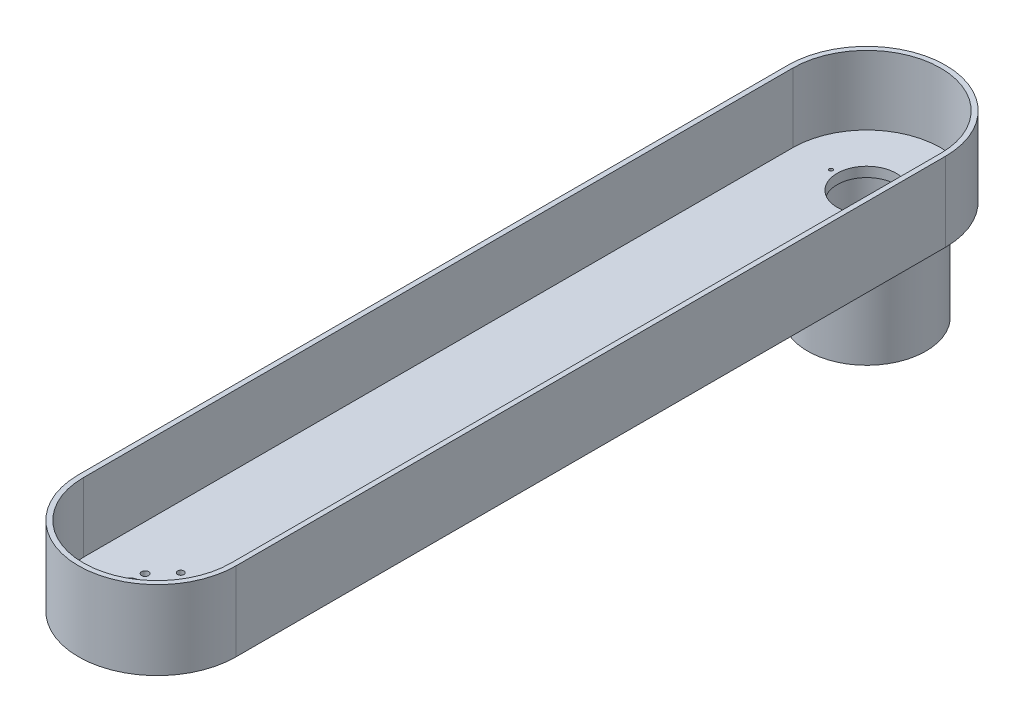
SolidWorks part; units mm, degrees
material "ABS"
ref_plane "Front Plane" through (0, 0, 0) normal (0, 0, 1) x (1, 0, 0)
ref_plane "Top Plane" through (0, 0, 0) normal (0, 1, 0) x (1, 0, 0)
ref_plane "Right Plane" through (0, 0, 0) normal (1, 0, 0) x (0, 0, -1)
sketch "Sketch1" plane through (0, 0, 0) normal (0, 1, 0) x (1, 0, 0)
  circle A0 centre (0, 0) radius 34.925
  circle A1 centre (0, 0) radius 38.1
  dimension "D1" = 69.85
  dimension "D2" = 3.175
extrude "Boss-Extrude1" add sketch "Sketch1" along normal blind 51.435
sketch "Sketch6" plane through (0, 0, 0) normal (0, -1, 0) x (1, 0, 0)
  circle A2 centre (0, 0) radius 34.925
  circle A3 centre (0, 0) radius 34.925
  circle A5 centre (0, 0) radius 38.1
  circle A6 centre (0, 0) radius 38.1
  dimension "D1" = 0
  dimension "D2" = 0
extrude "Boss-Extrude5" add sketch "Sketch6" along normal blind 6.096
ref_plane "Plane2" through (0, 23.114, 0) normal (0, -1, 0) x (1, 0, 0)
sketch "Sketch12" plane through (0, 23.114, 0) normal (0, -1, 0) x (1, 0, 0)
  circle A0 centre (0, 0) radius 25.4
  circle A5 centre (0, 0) radius 34.925
  dimension "D1" = 50.8
  dimension "D2" = 69.85
extrude "Boss-Extrude8" add sketch "Sketch12" against normal up to surface (28.321 mm away) up to face at (0, 51.435, 38.1)
sketch "Sketch2" plane through (0, 51.435, 0) normal (0, 1, 0) x (1, 0, 0)
  circle A0 centre (0, 0) radius 19.05
  circle A3 centre (0, 0) radius 38.1
  circle A4 centre (0, 0) radius 38.1
  dimension "D1" = 38.1
  dimension "D2" = 0
extrude "Boss-Extrude2" add sketch "Sketch2" along normal blind 6.35
ref_plane "Plane1" through (0, 26.67, 0) normal (0, -1, 0) x (1, 0, 0)
sketch "Sketch4" plane through (0, 26.67, 0) normal (0, -1, 0) x (1, 0, 0)
  circle A0 centre (0, 0) radius 26.9494
  dimension "D1" = 53.8988
extrude "Cut-Extrude1" cut sketch "Sketch4" along normal blind 1.7272
sketch "Sketch5" plane through (0, 57.785, 0) normal (0, 1, 0) x (1, 0, 0)
  line L0 (0, 0) -> (0, 12.0132) construction
  circle A0 centre (-23.0124, 0) radius 1.1303
  circle A1 centre (23.0124, 0) radius 1.1303
  dimension "D1" = 2.2606
  dimension "D2" = 46.0248
  dimension "D3" = 23.0124
extrude "Cut-Extrude5" cut sketch "Sketch5" against normal through all
cosmetic thread "Cosmetic Thread1" parameters "D2"=2.8448
cosmetic thread "Cosmetic Thread2" parameters "D2"=2.8448
sketch "Sketch7" plane through (0, 57.785, 0) normal (0, 1, 0) x (1, 0, 0)
  line L2 (-50.8, 0) -> (-50.8, -457.2)
  line L4 (50.8, 0) -> (50.8, -457.2)
  arc A0 (50.8, 0) -> (-50.8, 0) centre (0, 0) ccw
  arc A1 (-50.8, -457.2) -> (50.8, -457.2) centre (0, -457.2) ccw
  circle A5 centre (0, 0) radius 38.1
  circle A6 centre (0, 0) radius 38.1
  dimension "D1" = 101.6
  dimension "D2" = 457.2
  dimension "D3" = 0
extrude "Boss-Extrude6" add sketch "Sketch7" along normal blind 44.45 and the other way blind 6.35 separate body
shell "Shell3" thickness 3.175 removed face at (0, 102.235, 228.6)
sketch "Sketch11" plane through (0, 57.785, 0) normal (0, 1, 0) x (1, 0, 0)
  circle A2 centre (0, 0) radius 41.275
  circle A3 centre (0, 0) radius 41.275
  dimension "D1" = 0
extrude "Cut-Extrude4" cut sketch "Sketch11" along normal through all
combine bodies "Combine2" operation type add bodies to combine 116 120
sketch "Sketch13" plane through (0, 51.435, 0) normal (0, -1, 0) x (1, 0, 0)
  circle A0 centre (0, 457.2) radius 11
  circle A1 centre (0, 457.2) radius 21.5 construction
  circle A2 centre (0, 478.7) radius 2.25
  circle A3 centre (18.6195, 446.45) radius 2.25
  circle A4 centre (-18.6195, 446.45) radius 2.25
  circle A5 centre (0, 457.2) radius 17.5 construction
  circle A6 centre (-17.5, 457.2) radius 6
  circle A7 centre (17.5, 457.2) radius 6
  dimension "D1" = 22
  dimension "D2" = 43
  dimension "D3" = 4.5
  dimension "D5" = 35
  dimension "D6" = 12
  dimension "D7" = 12
  dimension "D4" = 3
extrude "Cut-Extrude6" cut sketch "Sketch13" against normal through all
sketch "Sketch15" plane through (0, 51.435, 0) normal (0, -1, 0) x (1, 0, 0)
  circle A2 centre (-17.5, 457.2) radius 6
  circle A3 centre (-17.5, 457.2) radius 6
  circle A5 centre (17.5, 457.2) radius 6
  circle A6 centre (17.5, 457.2) radius 6
  dimension "D1" = 0
  dimension "D2" = 0
extrude "Extrude-Thin1" add sketch "Sketch15" against normal up to surface (6.35 mm away) from offset 3.5 thin up to face at (17.5, 57.785, 463.2) offset against normal yes thin type one direction reverse wall 1
chamfer "Chamfer1" distance 2.3 angle 45 3 edges at (18.6195, 51.435, 444.2) (-18.6195, 51.435, 444.2) (0, 51.435, 476.45)
sketch "Sketch16" plane through (0, 51.435, 0) normal (0, -1, 0) x (1, 0, 0)
  circle A0 centre (-7.62, 479.9584) radius 2.0193
  circle A1 centre (7.62, 480.06) radius 2.0193
  circle A2 centre (7.62, 434.34) radius 2.0193
  circle A3 centre (-7.62, 434.4416) radius 2.0193
  dimension "D1" = 4.0386
extrude "Cut-Extrude7" cut sketch "Sketch16" against normal through all
cosmetic thread "Cosmetic Thread3" parameters "D2"=4.826
cosmetic thread "Cosmetic Thread4" parameters "D2"=4.826
cosmetic thread "Cosmetic Thread5" parameters "D2"=4.826
cosmetic thread "Cosmetic Thread6" parameters "D2"=4.826
sketch "Sketch17" plane through (0, -6.096, 0) normal (0, -1, 0) x (1, 0, 0)
  circle A0 centre (0, 0) radius 34.925
  circle A1 centre (0, 0) radius 38.1
extrude "Boss-Extrude9" add sketch "Sketch17" along normal blind 6.858
sketch "Sketch18" plane through (0, 57.785, 0) normal (0, 1, 0) x (1, 0, 0)
  line L0 (11, -457.2) -> (0, -457.2) construction
  line L1 (0, -457.2) -> (0, -462.2033) construction
  circle A0 centre (0, -457.2) radius 11 construction
